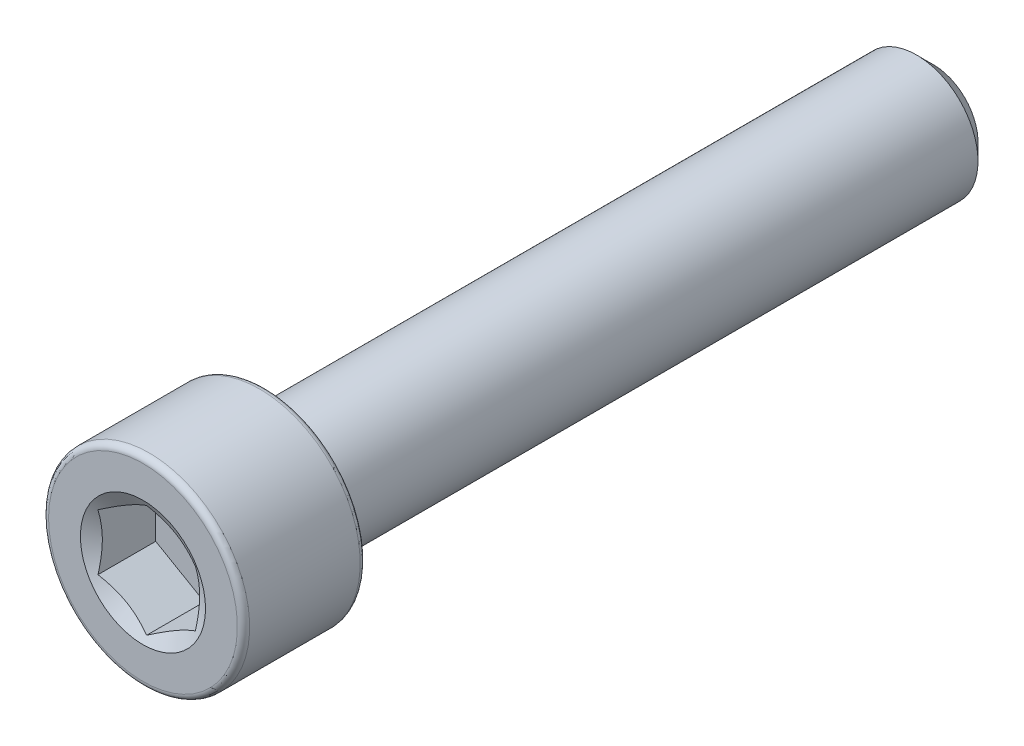
SolidWorks part; units mm, degrees
material "Alloy Steel (SS)"
ref_plane "Front Plane" through (0, 0, 0) normal (0, 0, 1) x (1, 0, 0)
ref_plane "Top Plane" through (0, 0, 0) normal (0, 1, 0) x (1, 0, 0)
ref_plane "Right Plane" through (0, 0, 0) normal (1, 0, 0) x (0, 0, -1)
sketch "Sketch1" plane through (0, 0, 0) normal (1, 0, 0) x (0, 0, -1)
  line L0 (11.2776, 0) -> (-11.2776, 0) construction
  line L1 (-7.7724, 2.8702) -> (-7.7724, -2.8702) construction
  line L2 (11.2776, 1.7526) -> (11.2776, -1.7526) construction
  line L3 (11.228, 1.8385) -> (11.6249, 1.1511) construction
  line L4 (11.5753, 1.237) -> (11.6745, 1.237) construction
  line L5 (11.6249, 1.1511) -> (12.0217, 1.8385) construction
  line L6 (12.0217, 1.8385) -> (11.228, 1.8385) construction
  line L7 (11.6249, 1.237) -> (11.6249, 1.1511) construction
  line L8 (11.6249, 1.8385) -> (11.6249, 1.7526) construction
  line L9 (11.9721, 1.7526) -> (11.2776, 1.7526) construction
  point P4 (-7.7724, 0)
  point P6 (-7.7724, 1.3891)
  point P7 (9.2932, -1.7526)
  point P20 (11.6249, 1.7956)
  dimension "Head Height" = 3.5052
  dimension "Head Diameter" = 5.7404
  dimension "Drive Size" = 2.7781
  dimension "Length" = 19.05
  dimension "Screw Size Decimal Equivalent" = 3.5052
  dimension "Pitch" = 0.7937
  dimension "Pitch/8" = 0.0992
  dimension "Thread Note" = 1.9844
sketch "Sketch2" plane through (0, 0, 0) normal (1, 0, 0) x (0, 0, -1)
  line L0 (11.2776, 0) -> (11.2776, 1.2764)
  line L1 (11.2776, 1.7526) -> (11.2776, -1.7526) construction
  line L2 (11.2776, 1.2764) -> (10.8014, 1.7526)
  line L3 (10.8014, 1.7526) -> (-7.7724, 1.7526)
  line L4 (-7.7724, 1.7526) -> (-7.7724, 2.6949)
  line L5 (-7.9477, 2.8702) -> (-11.1023, 2.8702)
  line L6 (-11.2776, 2.6949) -> (-11.2776, 0)
  line L7 (11.2776, 0) -> (-11.2776, 0) construction
  line L8 (-11.2776, 0) -> (11.2776, 0)
  arc A0 (-7.7724, 2.6949) -> (-7.9477, 2.8702) centre (-7.9477, 2.6949) ccw
  arc A1 (-11.1023, 2.8702) -> (-11.2776, 2.6949) centre (-11.1023, 2.6949) ccw
  point P19 (-7.7724, 2.8702)
  dimension "D3" = 0.1753
  dimension "D1" = 0.4762
  dimension "D2" = 45
revolve "Revolve1" add sketch "Sketch2" angle 360 about L0
sketch "Sketch3" plane through (0, 0, 0) normal (0, 0, 1) x (1, 0, 0)
  line L1 (-1.3891, 0.802) -> (-1.3891, -0.802)
  line L2 (-1.3891, -0.802) -> (0, -1.604)
  line L3 (0, -1.604) -> (1.3891, -0.802)
  line L4 (1.3891, -0.802) -> (1.3891, 0.802)
  line L5 (1.3891, 0.802) -> (0, 1.604)
  line L6 (0, 1.604) -> (-1.3891, 0.802)
  circle A0 centre (0, 0) radius 1.3891 construction
  circle A1 centre (0, 0) radius 2.8702 construction
extrude "Cut-Extrude1" cut sketch "Sketch3" against normal blind 1.7526 from vertex starting at point (0, 0, 11.2776)
sketch "Sketch4" plane through (0, 0, 11.2776) normal (0, 0, 1) x (1, 0, 0)
  line L0 (0, 1.604) -> (0, 1.9676) construction
  line L1 (0, 1.9676) -> (0, 2.3313) construction
  line L2 (0, 2.3313) -> (0, 2.6949) construction
  circle A0 centre (0, 0) radius 1.7858
  point P12 (0, 1.7858)
extrude "Cut-Extrude2" cut sketch "Sketch4" against normal through all draft 60
split "Split1" [suppressed] bodies to split 106 112
sketch "Sketch5" [suppressed] plane through (0, 0, 0) normal (1, 0, 0) x (0, 0, -1)
  line L0 (11.5753, 1.237) -> (11.6745, 1.237)
  line L1 (11.6745, 1.237) -> (11.9969, 1.7956)
  line L2 (11.9969, 1.7956) -> (11.2528, 1.7956)
  line L3 (11.2528, 1.7956) -> (11.5753, 1.237)
  line L4 (11.228, 1.8385) -> (11.6249, 1.1511) construction
sketch "Sketch6" [suppressed] plane through (0, 0, -11.2776) normal (0, 0, -1) x (-1, 0, 0)
  circle A0 centre (0, 0) radius 1.7526
curve "Helix/Spiral1" [suppressed] pitch 0.7937 height 19.8438 turns 25
sweep "Cut-Sweep1" [suppressed] cut profiles "Sketch5" path "Helix/Spiral1"
sketch "Sketch7" [suppressed] plane through (0, 0, 7.7724) normal (0, 0, -1) x (-1, 0, 0)
  circle A0 centre (0, 0) radius 1.8034
  circle A1 centre (0, 0) radius 1.7526 construction
  dimension "D1" = 0.0508
extrude "Boss-Extrude1" [suppressed] add sketch "Sketch7" along normal blind 2.3813 draft 20 and the other way blind 0.3505
ref_plane "Plane1" [suppressed] through (0, 0, 8.9291) normal (0, 0, -1) x (-1, 0, 0)
sketch "Sketch13" [suppressed] plane through (0, 0, 8.9291) normal (0, 0, -1) x (-1, 0, 0)
  line L0 (0.0718, 2.8693) -> (0, 0) construction
  line L1 (0, 0) -> (-0.0718, 2.8693) construction
  line L3 (0.0706, 2.8219) -> (0.0718, 2.8693)
  line L6 (-0.0706, 2.8219) -> (-0.0718, 2.8693)
  arc A1 (0.0718, 2.8693) -> (-0.0718, 2.8693) centre (0, 0) ccw
  circle A2 centre (0, 0) radius 2.8702 construction
  arc A3 (0.0706, 2.8219) -> (-0.0706, 2.8219) centre (0, 0) ccw
  point P2 (0, 2.8702)
  dimension "D3" = 0.0474
  dimension "D1" = 0.1435
extrude "Cut-Extrude3" [suppressed] cut sketch "Sketch13" against normal blind 1.9559
chamfer "Chamfer3" [suppressed] distance 0.0474 angle 60
chamfer "Chamfer4" [suppressed] distance 0.0474 angle 85
pattern_circular "CirPattern2" [suppressed] count 50 over 360 about axis through (0, 0, -11.2776) along (0, 0, 1) of bodies 134
equation "\"Pitch/8@Sketch1\" = \"Pitch@Sketch1\" / 8"
equation "\"Thread Note@Sketch1\"=\"Pitch@Sketch1\" * 2.5"
equation "\"D1@Sketch2\"=\"Pitch@Sketch1\"*.60"
equation "\"D3@Sketch2\"=\"Head Height@Sketch1\"*.05"
equation "\"D1@Cut-Extrude1\" = \"Head Height@Sketch1\" * .5"
equation "\"D3@Helix/Spiral1\" = \"Length@Sketch1\" + \"Pitch@Sketch1\""
equation "\"D4@Helix/Spiral1\" = \"Pitch@Sketch1\""
equation "\"D2@Boss-Extrude1\" = \"Head Height@Sketch1\" * .1"
equation "\"D1\"= \"Screw Size Decimal Equivalent@Sketch1\" * .4"
equation "\"D1@Plane1\"=\"Head Height@Sketch1\" * .33"
equation "\"D1@Cut-Extrude3\"=( \"Head Height@Sketch1\" - \"D1@Plane1\" - \"D3@Sketch2\" )  * .9"
equation "\"D1@Chamfer3\"=\"D3@Sketch13\""
equation "\"D1@Chamfer4\"=\"D3@Sketch13\""
equation "\"D1@CirPattern2\"=( \"Head Diameter@Sketch1\" * pi )  /  ( 2.5*\"D1@Sketch13\" )"
equation "\"D1@Sketch13\"=\"Head Diameter@Sketch1\" * .025"
equation "\"D3@Sketch13\"=\"D1@Sketch13\"*.33"
equation "\"D1@Boss-Extrude1\"=\"Pitch@Sketch1\"*3"
